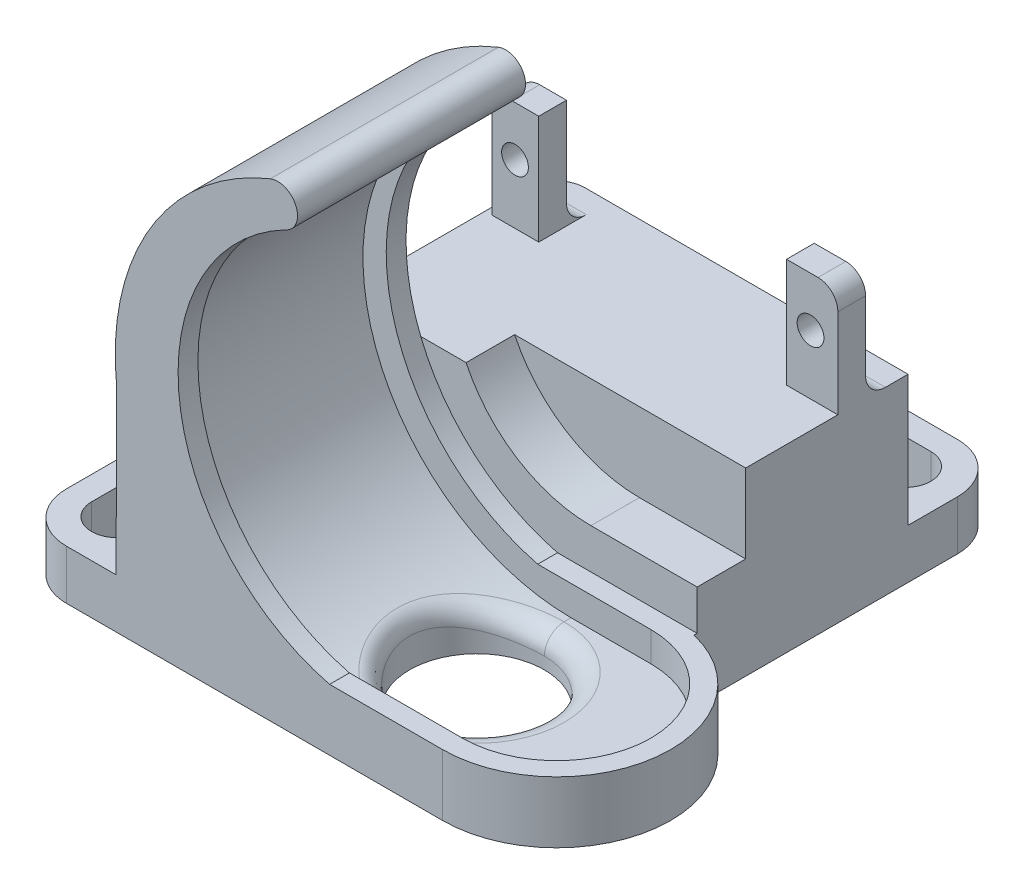
SolidWorks part; units mm, degrees
material "ABS"
ref_plane "Front Plane" through (0, 0, 0) normal (0, 0, 1) x (1, 0, 0)
ref_plane "Top Plane" through (0, 0, 0) normal (0, 1, 0) x (1, 0, 0)
ref_plane "Right Plane" through (0, 0, 0) normal (1, 0, 0) x (0, 0, -1)
sketch "Sketch1" plane through (0, 0, 0) normal (0, 1, 0) x (1, 0, 0)
  line L1 (-31.75, -12.065) -> (31.75, -12.065)
  line L2 (-31.75, -12.065) -> (-31.75, 12.065)
  line L3 (-31.75, 12.065) -> (31.75, 12.065)
  line L4 (31.75, -12.065) -> (31.75, 12.065)
  line L5 (-31.75, -12.065) -> (31.75, 12.065) construction
  line L6 (-31.75, 12.065) -> (31.75, -12.065) construction
  point P0 (0, 0)
  dimension "D1" = 24.13
  dimension "D2" = 63.5
extrude "Boss-Extrude1" add sketch "Sketch1" along normal blind 4.064
sketch "Sketch2" plane through (0, 0, 0) normal (0, 0, 1) x (1, 0, 0)
  line L0 (0, -2.2352) -> (0, 2.2352) construction
  line L1 (-31.75, 4.064) -> (31.75, 4.064) construction
  line L3 (-31.75, 4.064) -> (31.75, 4.064) construction
  line L4 (0, 4.064) -> (-26.7168, 4.064)
  line L5 (-31.571, 27.3677) -> (-26.7168, 4.064)
  arc A0 (-9.9723, 55.4695) -> (0, 4.064) centre (0, 30.734) ccw
  arc A1 (-11.8717, 60.181) -> (-31.571, 27.3677) centre (0, 30.734) ccw
  arc A2 (-9.9723, 55.4695) -> (-11.8717, 60.181) centre (-10.922, 57.8252) ccw
  dimension "D1" = 53.34
  dimension "D2" = 63.5
  dimension "D3" = 10.922
  dimension "D4" = 23.3037
  dimension "D5" = 23.8039
extrude "Boss-Extrude2" add sketch "Sketch2" along normal up to surface and the other way up to surface up to face at (0, 2.032, 12.065) other way up to face at (0, 2.032, -12.065)
sketch "Sketch4" plane through (0, 4.064, 0) normal (0, 1, 0) x (1, 0, 0)
  circle A0 centre (0, 0) radius 8.636
  dimension "D1" = 17.272
extrude "Cut-Extrude1" cut sketch "Sketch4" against normal through all and the other way blind 4.064
fillet "Fillet1" radius 2.54 2 edges at (8.636, 4.064, 0) (-8.5992, 5.4884, 0.7963)
sketch "Sketch6" plane through (0, 0, 12.065) normal (0, 0, 1) x (1, 0, 0)
  line L0 (-31.75, 4.064) -> (-26.7168, 4.064)
  line L1 (-26.7168, 4.064) -> (-25.8702, 0)
  line L2 (-25.8702, 0) -> (-31.75, 0)
  line L3 (-31.75, 4.064) -> (-31.75, 0) construction
  line L4 (-31.75, 0) -> (-31.75, 4.064)
  dimension "D1" = 4.1512
extrude "Cut-Extrude2" cut sketch "Sketch6" against normal through all
sketch "Sketch8" plane through (0, 0, 12.065) normal (0, 0, 1) x (1, 0, 0)
  line L0 (31.75, 0) -> (31.75, 7.874)
  line L1 (0, 4.064) -> (31.75, 4.064) construction
  line L2 (31.75, 0) -> (-25.8702, 0)
  line L3 (-25.8702, 0) -> (-31.571, 27.3677)
  line L4 (31.75, 7.874) -> (-23.9497, 7.874) construction
  line L5 (-4.2746, 7.874) -> (31.75, 7.874)
  arc A0 (-31.571, 27.3677) -> (-11.8717, 60.181) centre (0, 30.734) cw
  arc A1 (-11.8717, 60.181) -> (-9.9723, 55.4695) centre (-10.922, 57.8252) cw
  arc A2 (-9.9723, 55.4695) -> (-4.2746, 7.874) centre (1.9655, 32.7598) ccw
  dimension "D1" = 3.81
extrude "Boss-Extrude3" add sketch "Sketch8" along normal blind 2.54
sketch "Sketch9" plane through (0, 0, -12.065) normal (0, 0, -1) x (-1, 0, 0)
  line L0 (-31.75, 0) -> (-31.75, 7.874)
  line L1 (-31.75, 7.874) -> (4.2746, 7.874)
  line L2 (-31.75, 0) -> (25.8702, 0)
  line L3 (25.8702, 0) -> (31.571, 27.3677)
  arc A0 (31.571, 27.3677) -> (11.8717, 60.181) centre (0, 30.734) ccw
  arc A2 (9.9723, 55.4695) -> (4.2746, 7.874) centre (-1.9655, 32.7598) cw
  arc A3 (11.8717, 60.181) -> (9.9723, 55.4695) centre (10.922, 57.8252) ccw
extrude "Boss-Extrude4" add sketch "Sketch9" along normal blind 2.54
sketch "Sketch10" plane through (0, 4.064, 0) normal (0, 1, 0) x (1, 0, 0)
  line L0 (10.2183, 14.605) -> (10.2183, -14.605) construction
  line L3 (-4.2746, 14.605) -> (31.75, 14.605) construction
  line L4 (31.75, -14.605) -> (-4.2746, -14.605) construction
  line L5 (10.2183, 14.605) -> (10.2183, 12.065)
  line L6 (10.2183, -12.065) -> (10.2183, -14.605)
  arc A2 (10.2183, 14.605) -> (10.2183, -14.605) centre (10.2183, 0) cw
  arc A3 (10.2183, -12.065) -> (10.2183, 12.065) centre (10.2183, 0) ccw
extrude "Boss-Extrude5" add sketch "Sketch10" along normal blind 3.81
sketch "Sketch11" plane through (0, 7.874, 0) normal (0, 1, 0) x (1, 0, 0)
  line L0 (10.2183, 12.065) -> (10.2183, -12.065) construction
  line L1 (10.2183, 14.605) -> (10.2183, -14.605) construction
  line L2 (-4.2746, 14.605) -> (31.75, 14.605) construction
  line L3 (31.75, -14.605) -> (-4.2746, -14.605) construction
  line L4 (10.2183, 14.605) -> (31.75, 14.605)
  line L5 (31.75, 14.605) -> (31.75, -14.605)
  line L6 (31.75, -14.605) -> (10.2183, -14.605)
  arc A0 (10.2183, -14.605) -> (10.2183, 14.605) centre (10.2183, 0) ccw
extrude "Cut-Extrude3" cut sketch "Sketch11" against normal through all
sketch "Sketch12" plane through (0, 0, 0) normal (0, -1, 0) x (1, 0, 0)
  line L0 (-25.8702, -14.605) -> (-31.571, -14.605) construction
  line L1 (-31.2166, -14.605) -> (13.6144, -14.605)
  line L2 (-31.2166, -14.605) -> (-31.2166, -41.632)
  line L3 (-31.2166, -41.632) -> (13.6144, -41.632)
  line L4 (13.6144, -14.605) -> (13.6144, -41.632)
extrude "Boss-Extrude6" add sketch "Sketch12" against normal up to surface (23.114 mm away) up to face at (-6.2783, 14.6544, 12.065)
sketch "Sketch13" plane through (0, 0, 0) normal (0, -1, 0) x (1, 0, 0)
  line L0 (10.2183, -14.605) -> (13.6144, -14.605)
  line L1 (13.6144, -14.605) -> (13.6144, -13.3355)
  line L2 (13.6144, -13.3355) -> (10.2183, -14.605)
extrude "Boss-Extrude7" add sketch "Sketch13" against normal up to surface (7.874 mm away) up to face at (6.3056, 7.874, 0)
sketch "Sketch14" plane through (0, 0, -14.605) normal (0, 0, 1) x (1, 0, 0)
  line L0 (0, 13.0173) -> (18.6203, 13.0173)
  line L1 (18.6203, 13.0173) -> (17.7167, 30.734)
  arc A0 (17.7167, 30.734) -> (0, 13.0173) centre (0, 30.734) ccw
extrude "Cut-Extrude4" cut sketch "Sketch14" against normal up to surface (6.2198 mm away) up to face at (7.2796, 4.064, 0)
sketch "Sketch16" plane through (0, 0, -14.605) normal (0, 0, 1) x (1, 0, 0)
  line L0 (-31.2166, 23.114) -> (-30.685, 23.114)
  line L1 (-30.685, 23.114) -> (-25.8702, 0)
  line L2 (-25.8702, 0) -> (-31.2166, 0)
  line L3 (-31.2166, 0) -> (-31.2166, 23.114)
extrude "Cut-Extrude5" cut sketch "Sketch16" against normal up to surface (27.027 mm away) up to face at (-8.8011, 11.557, -41.632)
sketch "Sketch17" plane through (0, 23.114, 0) normal (0, 1, 0) x (1, 0, 0)
  line L0 (13.6144, 41.632) -> (13.6144, 20.8248) construction
  line L1 (6.6167, 32.6358) -> (13.6144, 32.6358)
  line L2 (6.6167, 32.6358) -> (6.6167, 36.1918)
  line L3 (6.6167, 36.1918) -> (13.6144, 36.1918)
  line L4 (13.6144, 32.6358) -> (13.6144, 36.1918)
  dimension "D1" = 3.556
extrude "Boss-Extrude8" add sketch "Sketch17" along normal blind 13.97
sketch "Sketch18" plane through (0, 23.114, 0) normal (0, 1, 0) x (1, 0, 0)
  line L0 (-30.685, 41.632) -> (-30.685, 14.605) construction
  line L1 (-24.2951, 32.6358) -> (-30.685, 32.6358)
  line L2 (-24.2951, 32.6358) -> (-24.2951, 36.1918)
  line L3 (-24.2951, 36.1918) -> (-30.685, 36.1918)
  line L4 (-30.685, 32.6358) -> (-30.685, 36.1918)
  dimension "D1" = 3.556
extrude "Boss-Extrude9" add sketch "Sketch18" along normal blind 13.97
sketch "Sketch19" plane through (0, 37.084, 0) normal (0, 1, 0) x (1, 0, 0)
  line L0 (-24.2951, 36.1918) -> (6.6167, 36.1918) construction
  line L1 (6.6167, 32.6358) -> (13.6144, 32.6358) construction
  line L2 (-24.7142, 39.7478) -> (7.0358, 39.7478)
  line L3 (-24.7142, 39.7478) -> (-24.7142, 32.6358)
  line L4 (-24.7142, 32.6358) -> (7.0358, 32.6358)
  line L5 (7.0358, 39.7478) -> (7.0358, 32.6358)
  line L6 (-24.7142, 39.7478) -> (7.0358, 32.6358) construction
  line L7 (-24.7142, 32.6358) -> (7.0358, 39.7478) construction
  point P4 (-8.8392, 36.1918)
  dimension "D1" = 31.75
extrude "Cut-Extrude6" cut sketch "Sketch19" against normal up to surface (13.97 mm away) up to face at (-10.4957, 23.114, -29.6026)
sketch "Sketch20" plane through (0, 0, -36.1918) normal (0, 0, -1) x (-1, 0, 0)
  circle A0 centre (27.7559, 30.734) radius 1.7145
  circle A1 centre (-10.1155, 30.734) radius 1.7145
  dimension "D1" = 3.429
  dimension "D2" = 3.429
extrude "Cut-Extrude7" cut sketch "Sketch20" against normal up to surface (3.556 mm away)
fillet "Fillet2" radius 2.54 1 edges at (10.3251, 23.114, -36.1918)
fillet "Fillet3" radius 2.54 1 edges at (-27.6996, 23.114, -36.1918)
fillet "Fillet4" radius 2.54 2 edges at (13.6144, 37.084, -34.4138) (-30.685, 37.084, -34.4138)
ref_plane "Plane1" through (-31.571, 0, 0) normal (1, 0, 0) x (0, 0, -1)
ref_plane "Plane2" through (0, 0, 0) normal (0, -1, 0) x (-1, 0, 0)
ref_plane "Plane3" through (0, 0, 14.605) normal (0, 0, 1) x (1, 0, 0)
sketch "Sketch26" plane through (0, 0, 14.605) normal (0, 0, 1) x (1, 0, 0)
  line L0 (-25.8702, 0) -> (-31.6536, 0)
  line L1 (-31.6536, 0) -> (-31.571, 27.3677)
  line L2 (-31.571, 27.3677) -> (-25.8702, 0)
extrude "Boss-Extrude10" add sketch "Sketch26" against normal blind 29.21
sketch "Sketch22" plane through (0, 0, -14.605) normal (0, 0, -1) x (-1, 0, 0)
  line L0 (30.685, 23.114) -> (31.5839, 23.114)
  line L1 (31.571, 27.3677) -> (31.6536, 0) construction
  line L2 (31.5839, 23.114) -> (31.6536, 0)
  line L3 (31.6536, 0) -> (25.8702, 0)
  line L4 (25.8702, 0) -> (30.685, 23.114)
extrude "Boss-Extrude11" add sketch "Sketch22" along normal up to surface (27.027 mm away) up to face at (-7.3316, 11.557, -41.632)
sketch "Sketch23" plane through (0, 0, 0) normal (0, -1, 0) x (1, 0, 0)
  line L0 (-38.0036, 8.0765) -> (-38.0036, -35.1035) construction
  line L1 (-34.7016, 8.0765) -> (-34.7016, -35.1035)
  line L2 (-41.3056, 8.0765) -> (-41.3056, -35.1035)
  line L3 (-24.8597, -47.982) -> (6.8903, -47.982) construction
  line L4 (-24.8597, -44.68) -> (6.8903, -44.68)
  line L5 (-24.8597, -51.284) -> (6.8903, -51.284)
  line L6 (-15.5546, 14.605) -> (-44.3536, 14.605)
  line L7 (-44.3536, 14.605) -> (-44.3536, -41.632)
  line L8 (-31.6536, -41.632) -> (-31.6536, 14.605) construction
  line L9 (-31.5839, -54.3319) -> (-31.5839, -54.332)
  line L10 (-31.5839, -54.332) -> (13.6144, -54.332)
  line L11 (13.6144, -54.332) -> (13.6144, -35.1035)
  line L12 (-31.6536, -41.632) -> (13.6144, -41.632) construction
  line L14 (-15.5546, 14.605) -> (-15.5546, -35.1035)
  line L15 (-15.5546, -35.1035) -> (13.6144, -35.1035)
  arc A0 (-34.7016, 8.0765) -> (-41.3056, 8.0765) centre (-38.0036, 8.0765) ccw
  arc A1 (-41.3056, -35.1035) -> (-34.7016, -35.1035) centre (-38.0036, -35.1035) ccw
  arc A2 (-24.8597, -44.68) -> (-24.8597, -51.284) centre (-24.8597, -47.982) ccw
  arc A3 (6.8903, -51.284) -> (6.8903, -44.68) centre (6.8903, -47.982) ccw
  arc A5 (-44.3536, -41.632) -> (-31.5839, -54.3319) centre (-31.6536, -41.632) ccw
  point P2 (-38.0036, -13.5135)
  point P7 (-8.9847, -47.982)
  point P25 (-8.9847, -54.332)
  point P27 (-44.3536, -13.5135)
  line M19 (-31.6536, 14.605) -> (-31.6536, -41.632)
  line M20 (-31.6536, -41.632) -> (13.6144, -41.632)
  line M21 (13.6144, -41.632) -> (13.6144, -14.2047)
  arc M22 (13.6144, -14.2047) -> (10.2183, 14.605) centre (10.2183, 0) ccw
  line M23 (10.2183, 14.605) -> (-31.6536, 14.605)
  circle M24 centre (0, 0) radius 8.636
  dimension "D1" = 3.302
  dimension "D2" = 3.302
  dimension "D3" = 6.35
  dimension "D5" = 31.75
  dimension "D6" = 43.18
  dimension "D7" = 6.35
extrude "Boss-Extrude16" add sketch "Sketch23" against normal blind 6.35 contours L7 A5 L9 L10 L11 L6 A1 L2 A0 L1 A3 L5 A2 L4 M20 M19 | M23 M19 M20 M21 M22 M24 region at (-19.6707, 0, -17.8328) region at (-32.5543, 0, -13.5135)
fillet "Fillet5" radius 6.35 2 edges at (-44.3536, 3.175, 14.605) (13.6144, 3.175, -54.332)
fillet "Fillet6" radius 3.81 1 edges at (-31.6091, 14.732, -41.632)
